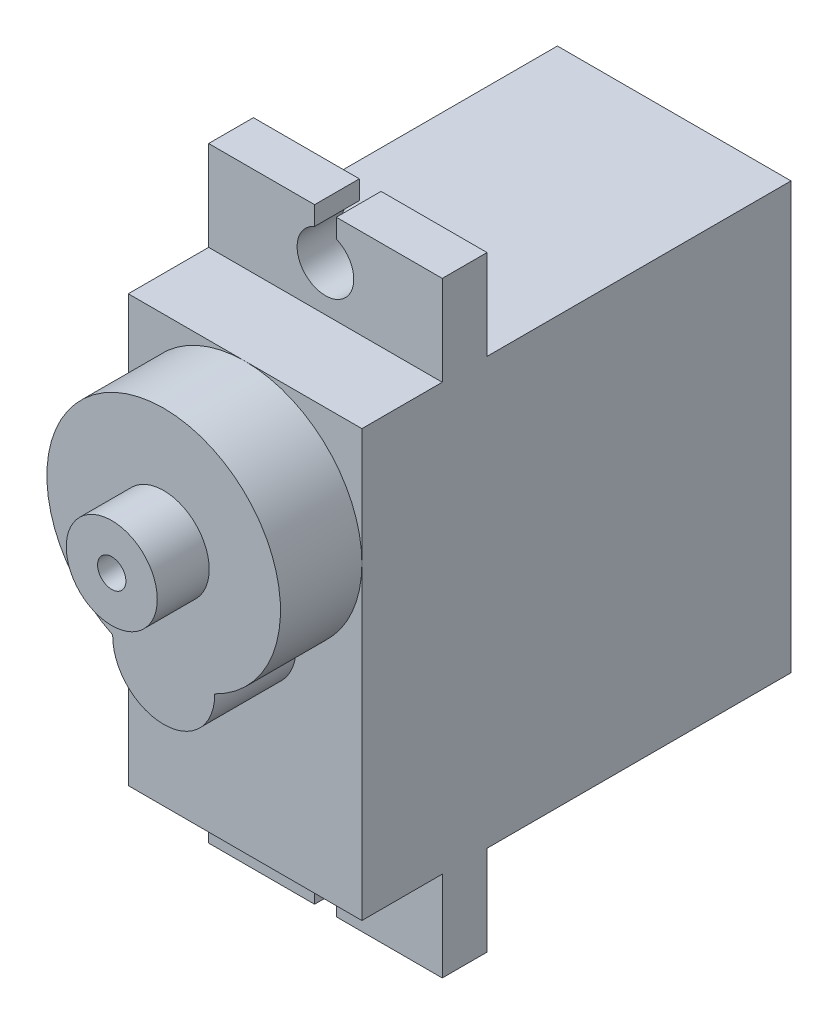
SolidWorks part; units mm, degrees
ref_plane "Front Plane" through (0, 0, 0) normal (0, 0, 1) x (1, 0, 0)
ref_plane "Top Plane" through (0, 0, 0) normal (0, 1, 0) x (1, 0, 0)
ref_plane "Right Plane" through (0, 0, 0) normal (1, 0, 0) x (0, 0, -1)
sketch "Sketch1" plane through (0, 0, 0) normal (0, 0, 1) x (1, 0, 0)
  line L1 (-6.1849, -11.2776) -> (6.1849, -11.2776)
  line L2 (-6.1849, -11.2776) -> (-6.1849, 11.2776)
  line L3 (-6.1849, 11.2776) -> (6.1849, 11.2776)
  line L4 (6.1849, -11.2776) -> (6.1849, 11.2776)
  line L5 (-6.1849, -11.2776) -> (6.1849, 11.2776) construction
  line L6 (-6.1849, 11.2776) -> (6.1849, -11.2776) construction
  point P0 (0, 0)
  dimension "D1" = 12.3698
  dimension "D2" = 22.5552
extrude "Boss-Extrude1" add sketch "Sketch1" along normal mid plane 22.7203
ref_plane "Plane1" through (0, 0, 7.1056) normal (0, 0, 1) x (1, 0, 0)
sketch "Sketch2" plane through (0, 0, 7.1056) normal (0, 0, 1) x (1, 0, 0)
  line L0 (-0.575, 16.0401) -> (-6.1849, 16.0401)
  line L1 (-6.1849, 16.0401) -> (-6.1849, 11.2776)
  line L2 (-6.1849, 11.2776) -> (6.1849, 11.2776)
  line L3 (6.1849, 11.2776) -> (6.1849, 16.0401)
  line L4 (6.1849, 16.0401) -> (0.575, 16.0401)
  line L5 (0.575, 16.0401) -> (0.575, 15.0401)
  line L6 (-0.575, 15.0401) -> (-0.575, 16.0401)
  line L7 (-1.5, 13.6547) -> (1.5, 13.6547) construction
  arc A0 (0.575, 15.0401) -> (-0.575, 15.0401) centre (0, 13.6547) cw
  dimension "D2" = 3
  dimension "D1" = 4.7625
  dimension "D3" = 1
  dimension "D4" = 1.15
extrude "Boss-Extrude2" add sketch "Sketch2" against normal blind 2.37
mirror "Mirror1" about plane through (0, 0, 0) normal (0, 1, 0) of "Boss-Extrude2"
sketch "Sketch3" plane through (0, 0, 11.3601) normal (0, 0, 1) x (1, 0, 0)
  line L0 (6.1849, 11.2776) -> (-6.1849, 11.2776) construction
  line L1 (6.1849, -11.2776) -> (6.1849, 11.2776) construction
  line L2 (2.7, -0.5224) -> (2.7, -0.4717)
  line L3 (-2.7, -0.5224) -> (-2.7, -0.4717)
  line L4 (0, 11.2776) -> (0, -3.2224) construction
  arc A0 (2.7, -0.4717) -> (-2.7, -0.4717) centre (0, 5.0927) ccw
  arc A1 (2.7, -0.5224) -> (-2.7, -0.5224) centre (0, -0.5224) cw
  dimension "D1" = 5.4
  dimension "D2" = 14.5
extrude "Boss-Extrude3" add sketch "Sketch3" along normal blind 4.31
sketch "Sketch4" plane through (0, 0, 15.6702) normal (0, 0, 1) x (1, 0, 0)
  circle A0 centre (0, 5.0927) radius 2.41
  circle A1 centre (0, 5.0927) radius 0.75
  dimension "D1" = 4.82
  dimension "D2" = 1.5
extrude "Boss-Extrude4" add sketch "Sketch4" along normal blind 2.75
ref_axis "Axis1" through (0, 5.0927, 22.3459) along (0, 0, -1)
